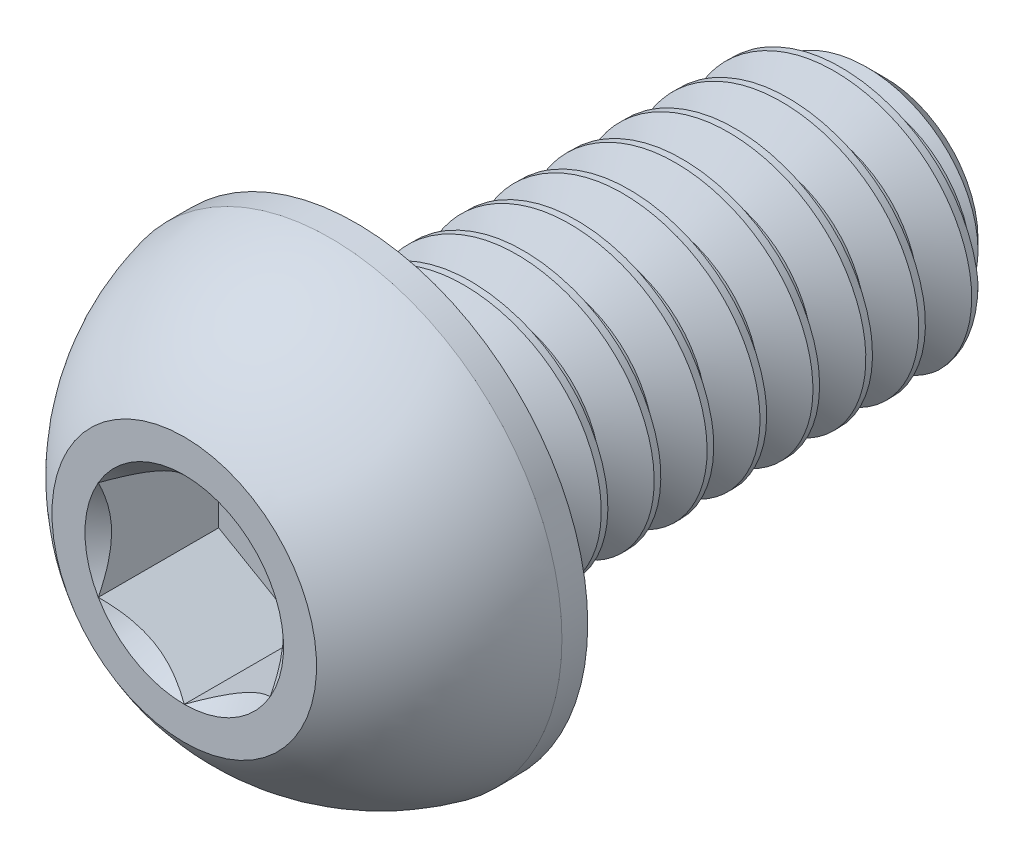
SolidWorks part; units mm, degrees
ref_plane "Front" through (0, 0, 0) normal (0, 0, 1) x (1, 0, 0)
ref_plane "Top" through (0, 0, 0) normal (0, 1, 0) x (1, 0, 0)
ref_plane "Right" through (0, 0, 0) normal (1, 0, 0) x (0, 0, -1)
sketch "Sketch1" plane through (0, 0, 0) normal (1, 0, 0) x (0, 0, -1)
  line L2 (1.3, 1) -> (5.3, 1)
  line L3 (5.3, 1) -> (5.3, 0)
  line L4 (5.3, 0) -> (1.3, 0)
  line L6 (1.105, 1.75) -> (1.3, 1.75) construction
  line L7 (5.3, 1) -> (5.3, -1) construction
  line L8 (0, 0) -> (1.3, 0) construction
  line L9 (1.3, 1.75) -> (1.3, -1.75) construction
  line L11 (1.3, 1) -> (1.3, 0)
  line L13 (0, 0.65) -> (0, -0.65) construction
  line L14 (0, 0.65) -> (0, 1) construction
  line L15 (5.275, 1.0433) -> (5.475, 0.6969) construction
  line L16 (5.475, 0.6969) -> (5.675, 1.0433) construction
  line L17 (5.675, 1.0433) -> (5.275, 1.0433) construction
  line L18 (5.3, 1) -> (5.65, 1) construction
  line L19 (5.475, 1.0433) -> (5.475, 1) construction
  line L20 (5.475, 1) -> (5.475, 0.7402) construction
  line L21 (5.475, 0.7402) -> (5.475, 0.6969) construction
  line L22 (5.45, 0.7402) -> (5.5, 0.7402)
  line L23 (5.2875, 1.0217) -> (5.6625, 1.0217)
  line L24 (5.5, 0.7402) -> (5.6625, 1.0217)
  line L25 (5.45, 0.7402) -> (5.2875, 1.0217)
  line L26 (5, 1) -> (5.3, 0.7)
  arc A3 (0, 1) -> (1.105, 1.75) centre (1.4858, 0) cw construction
  point P29 (5.475, 1.0217)
  point P30 (4.3, -1)
  dimension "D1" = 0.195
  dimension "Pitch" = 0.4
  dimension "D3" = 0.05
  dimension "D2" = 0.3
  dimension "D4" = 45
  dimension "D5" = 1
sketch "Sketch10" plane through (0, 0, 0) normal (1, 0, 0) x (0, 0, -1)
  line L0 (5, 1) -> (5.3, 0.7) construction
  line L1 (5, 1) -> (5.3, 0.7)
  line L4 (5.3, 1) -> (1.3, 1)
  line L5 (5.3, 0) -> (5.3, 1)
  line L6 (1.3, 0) -> (5.3, 0)
  line L7 (1.3, 1) -> (1.3, 0)
  line L8 (5, 1) -> (1.3, 1)
  line L9 (5.3, 0) -> (5.3, 0.7)
  line L10 (1.3, 0) -> (5.3, 0)
  line L11 (1.3, 1) -> (1.3, 0)
  dimension "D1" = 0
revolve "Revolve3" add sketch "Sketch10" angle 360 about L8
sketch "Sketch7" plane through (0, 0, 0) normal (1, 0, 0) x (0, 0, -1)
  line L6 (1.105, 1.75) -> (1.3, 1.75) construction
  line L8 (0, 0) -> (1.3, 0) construction
  line L11 (1.3, 1.75) -> (1.3, -1.75) construction
  line L12 (1.105, 1.75) -> (1.3, 1.75)
  line L13 (0, 0) -> (1.3, 0)
  line L14 (0, 0.65) -> (0, -0.65) construction
  line L15 (1.3, 1.75) -> (1.3, 0)
  line L16 (0, 1) -> (0, 0)
  arc A2 (1.105, 1.75) -> (0, 1) centre (1.4858, 0) ccw construction
  arc A3 (1.105, 1.75) -> (0, 1) centre (1.4858, 0) ccw
revolve "Revolve2" add sketch "Sketch7" angle 360 mid plane about L13
sketch "Sketch5" plane through (0, 0, 0) normal (0, 0, 1) x (1, 0, 0)
  line L1 (0.65, -0.3753) -> (0.65, 0.3753)
  line L2 (0.65, 0.3753) -> (0, 0.7506)
  line L3 (0, 0.7506) -> (-0.65, 0.3753)
  line L4 (-0.65, 0.3753) -> (-0.65, -0.3753)
  line L5 (-0.65, -0.3753) -> (0, -0.7506)
  line L6 (0, -0.7506) -> (0.65, -0.3753)
  circle A0 centre (0, 0) radius 0.65 construction
extrude "Cut-Extrude2" cut sketch "Sketch5" against normal blind 0.91
sketch "Sketch6" plane through (0, 0, 0) normal (0, 0, 1) x (1, 0, 0)
  circle A0 centre (0, 0) radius 0.7506
extrude "Cut-Extrude3" cut sketch "Sketch6" against normal blind 0.91 draft 45
sketch "Sketch9" plane through (0, 0, -1.3) normal (0, 0, -1) x (-1, 0, 0)
  circle A0 centre (0, 0) radius 1 construction
  circle A4 centre (0, 0) radius 1
split "Split1" bodies to split 113 resulting bodies 123 124 split by face at (1.75, 0, -1.3)
sketch "Sketch11" plane through (0, 0, -5.3) normal (0, 0, -1) x (-1, 0, 0)
  circle A0 centre (0, 0) radius 1 construction
  circle A1 centre (0, 0) radius 1
curve "Helix/Spiral1" pitch 0.4 height 5.3 radius 1 centre (0, 0, -5.3) axis (0, 0, 1) start towards (0, 1, 0)
sketch "Sketch12" plane through (0, 0, 0) normal (1, 0, 0) x (0, 0, -1)
  line L0 (5.45, 0.7402) -> (5.5, 0.7402) construction
  line L1 (5.5, 0.7402) -> (5.6625, 1.0217) construction
  line L2 (5.2875, 1.0217) -> (5.6625, 1.0217) construction
  line L3 (5.45, 0.7402) -> (5.2875, 1.0217) construction
  line L4 (5.45, 0.7402) -> (5.5, 0.7402)
  line L5 (5.5, 0.7402) -> (5.6625, 1.0217)
  line L6 (5.2875, 1.0217) -> (5.6625, 1.0217)
  line L7 (5.45, 0.7402) -> (5.2875, 1.0217)
sweep "Cut-Sweep2" cut profiles "Sketch12" path "Helix/Spiral1" align with end faces yes
extrude "Boss-Extrude1" add sketch "Sketch9" along normal blind 10 draft 45
equation "\"D1@Cut-Extrude2\" = \"Head Ht@Sketch1\" * .7"
equation "\"D1@Sketch1\" = \"Head Ht@Sketch1\" * .15"
equation "\"D1@Cut-Extrude3\" = \"D1@Cut-Extrude2\""
equation "\"D3@Sketch1\" = \"Pitch@Sketch1\" / 8"
equation "\"D2@Sketch1\"=\"Pitch@Sketch1\"*0.75"
equation "\"D3@Helix/Spiral1\" = \"Lg@Sketch1\" + \"Head Ht@Sketch1\""
equation "\"D4@Helix/Spiral1\"=\"pitch@sketch1\""
equation "\"D5@Sketch1\"=\"Pitch@Sketch1\"*2.5"
